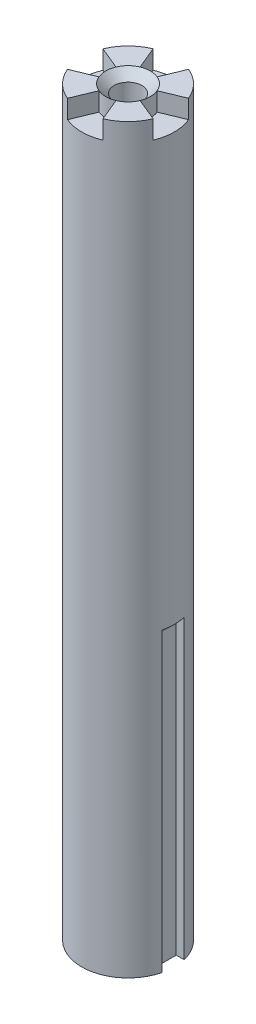
SolidWorks part; units mm, degrees
material "Cast Alloy Steel"
ref_plane "Front Plane" through (0, 0, 0) normal (0, 0, 1) x (1, 0, 0)
ref_plane "Top Plane" through (0, 0, 0) normal (0, 1, 0) x (1, 0, 0)
ref_plane "Right Plane" through (0, 0, 0) normal (1, 0, 0) x (0, 0, -1)
sketch "Sketch1" plane through (0, 0, 0) normal (0, 1, 0) x (1, 0, 0)
  circle A0 centre (0, 0) radius 6.35
  point P8 (0, -6.35)
  dimension "D1" = 12.7
extrude "Boss-Extrude1" add sketch "Sketch1" along normal blind 101.6
sketch "Sketch2" plane through (0, 0, 0) normal (0, -1, 0) x (-1, 0, 0)
  line L0 (-6.1644, -1.524) -> (-5.08, -1.524)
  line L1 (-5.08, -1.524) -> (-5.08, 1.524)
  line L2 (-5.08, 1.524) -> (-6.1644, 1.524)
  line L3 (0, 0) -> (6.35, 0) construction
  circle A0 centre (0, 0) radius 6.35 construction
  circle A1 centre (0, 0) radius 6.35 construction
  arc A3 (-6.1644, 1.524) -> (-6.1644, -1.524) centre (0, 0) ccw
  point P11 (6.35, 0)
  point P13 (-5.08, 0)
  dimension "D1" = 3.048
  dimension "D2" = 11.43
extrude "Cut-Extrude1" cut sketch "Sketch2" against normal blind 40.64
fillet "Fillet1" radius 1.27 1 edges at (5.08, 40.64, 0)
hole_wizard "#10-24 Tapped Hole1" positions "Sketch4" profile "Sketch5" tap size "#10-24" standard "ANSI Inch"
sketch "Sketch4" plane through (0, 101.6, 0) normal (0, 1, 0) x (1, 0, 0)
  point P0 (0, 0)
sketch "Sketch5" plane through (0, 101.6, 0) normal (1, 0, 0) x (0, 0, 1)
  line L0 (0, 0) -> (0, 14.0948)
  line L1 (0, 14.0948) -> (1.8986, 12.954)
  line L2 (1.8986, 12.954) -> (1.8986, 1.1494)
  line L3 (1.8986, 1.1494) -> (3.048, 0)
  line L5 (3.048, 0) -> (0, 0)
  line L6 (-1.8986, 1.1494) -> (-3.048, 0) construction
  line L10 (0, 14.0948) -> (-1.8987, 12.954) construction
  line L11 (0, -6.35) -> (0, 107.95) construction
  dimension "Tap Drill Dia." = 3.7973
  dimension "Tap Drill Depth" = 12.954
  dimension "Near C'Sink Dia." = 6.096
  dimension "Near C'Sink Angle" = 90
  dimension "Drill Angle" = 118
cosmetic thread "Hole Thread1" parameters "D1"=9.652, "D2"=4.826
sketch "Sketch6" plane through (0, 101.6, 0) normal (0, 1, 0) x (1, 0, 0)
  line L0 (2.43, -5.8666) -> (1.1664, -2.816)
  line L1 (-2.43, -5.8666) -> (-1.1664, -2.816)
  line L2 (-5.8666, 2.43) -> (-2.816, 1.1664)
  line L3 (-5.8666, -2.43) -> (-2.816, -1.1664)
  line L4 (2.43, 5.8666) -> (1.1664, 2.816)
  line L5 (-2.43, 5.8666) -> (-1.1664, 2.816)
  line L6 (5.8666, -2.43) -> (2.816, -1.1664)
  line L7 (5.8666, 2.43) -> (2.816, 1.1664)
  circle A0 centre (0, 0) radius 6.35 construction
  circle A1 centre (0, 0) radius 3.048 construction
  arc A2 (-2.43, -5.8666) -> (2.43, -5.8666) centre (0, 0) ccw
  arc A3 (-1.1664, -2.816) -> (1.1664, -2.816) centre (0, 0) ccw
  arc A4 (-2.816, 1.1664) -> (-2.816, -1.1664) centre (0, 0) ccw
  arc A5 (-5.8666, 2.43) -> (-5.8666, -2.43) centre (0, 0) ccw
  arc A6 (1.1664, 2.816) -> (-1.1664, 2.816) centre (0, 0) ccw
  arc A7 (2.43, 5.8666) -> (-2.43, 5.8666) centre (0, 0) ccw
  arc A8 (2.816, -1.1664) -> (2.816, 1.1664) centre (0, 0) ccw
  arc A9 (5.8666, -2.43) -> (5.8666, 2.43) centre (0, 0) ccw
  point P23 (0, 0)
  dimension "D1" = 45
  dimension "D2" = 4
extrude "Cut-Extrude3" cut sketch "Sketch6" against normal blind 2.54
